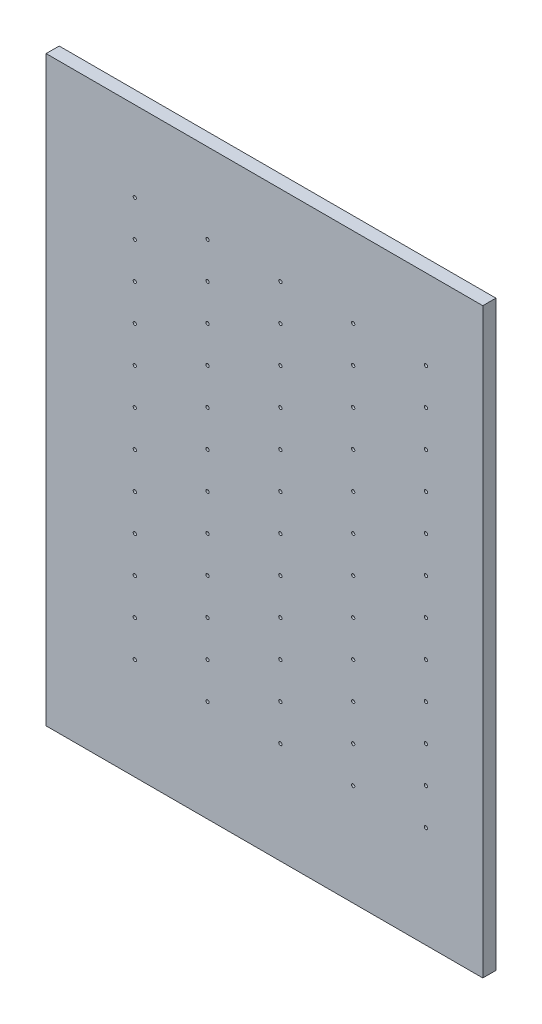
SolidWorks part; units mm, degrees
ref_plane "Спереди" through (0, 0, 0) normal (0, 0, 1) x (1, 0, 0)
ref_plane "Сверху" through (0, 0, 0) normal (0, 1, 0) x (1, 0, 0)
ref_plane "Справа" through (0, 0, 0) normal (1, 0, 0) x (0, 0, -1)
sketch "Эскиз1" plane through (0, 0, 0) normal (0, 0, 1) x (1, 0, 0)
  line L1 (0, 0) -> (600, 0)
  line L2 (0, 0) -> (0, 800)
  line L3 (0, 800) -> (600, 800)
  line L4 (600, 0) -> (600, 800)
extrude "Бобышка-Вытянуть1" add sketch "Эскиз1" along normal blind 18
sketch "Эскиз2" plane through (0, 0, 18) normal (0, 0, 1) x (1, 0, 0)
  circle A0 centre (521.8745, 139.7815) radius 2.25
  circle A1 centre (421.8745, 139.7815) radius 2.25
  circle A2 centre (321.8745, 139.7815) radius 2.25
  circle A3 centre (221.8745, 139.7815) radius 2.25
  circle A4 centre (121.8745, 139.7815) radius 2.25
  circle A5 centre (421.8745, 189.7815) radius 2.25
  circle A6 centre (321.8745, 189.7815) radius 2.25
  circle A7 centre (221.8745, 189.7815) radius 2.25
  circle A8 centre (121.8745, 189.7815) radius 2.25
  circle A9 centre (421.8745, 239.7815) radius 2.25
  circle A10 centre (321.8745, 239.7815) radius 2.25
  circle A11 centre (221.8745, 239.7815) radius 2.25
  circle A12 centre (121.8745, 239.7815) radius 2.25
  circle A13 centre (421.8745, 289.7815) radius 2.25
  circle A14 centre (321.8745, 289.7815) radius 2.25
  circle A15 centre (221.8745, 289.7815) radius 2.25
  circle A16 centre (121.8745, 289.7815) radius 2.25
  circle A17 centre (421.8745, 339.7815) radius 2.25
  circle A18 centre (321.8745, 339.7815) radius 2.25
  circle A19 centre (221.8745, 339.7815) radius 2.25
  circle A20 centre (121.8745, 339.7815) radius 2.25
  circle A21 centre (421.8745, 389.7815) radius 2.25
  circle A22 centre (321.8745, 389.7815) radius 2.25
  circle A23 centre (221.8745, 389.7815) radius 2.25
  circle A24 centre (121.8745, 389.7815) radius 2.25
  circle A25 centre (421.8745, 439.7815) radius 2.25
  circle A26 centre (321.8745, 439.7815) radius 2.25
  circle A27 centre (221.8745, 439.7815) radius 2.25
  circle A28 centre (121.8745, 439.7815) radius 2.25
  circle A29 centre (421.8745, 489.7815) radius 2.25
  circle A30 centre (321.8745, 489.7815) radius 2.25
  circle A31 centre (221.8745, 489.7815) radius 2.25
  circle A32 centre (121.8745, 489.7815) radius 2.25
  circle A33 centre (421.8745, 539.7815) radius 2.25
  circle A34 centre (321.8745, 539.7815) radius 2.25
  circle A35 centre (221.8745, 539.7815) radius 2.25
  circle A36 centre (121.8745, 539.7815) radius 2.25
  circle A37 centre (421.8745, 589.7815) radius 2.25
  circle A38 centre (321.8745, 589.7815) radius 2.25
  circle A39 centre (221.8745, 589.7815) radius 2.25
  circle A40 centre (121.8745, 589.7815) radius 2.25
  circle A41 centre (421.8745, 639.7815) radius 2.25
  circle A42 centre (321.8745, 639.7815) radius 2.25
  circle A43 centre (221.8745, 639.7815) radius 2.25
  circle A44 centre (121.8745, 639.7815) radius 2.25
  circle A45 centre (421.8745, 689.7815) radius 2.25
  circle A46 centre (321.8745, 689.7815) radius 2.25
  circle A47 centre (221.8745, 689.7815) radius 2.25
  circle A48 centre (121.8745, 689.7815) radius 2.25
  circle A49 centre (521.8745, 189.7815) radius 2.25
  circle A50 centre (521.8745, 239.7815) radius 2.25
  circle A51 centre (521.8745, 289.7815) radius 2.25
  circle A52 centre (521.8745, 339.7815) radius 2.25
  circle A53 centre (521.8745, 389.7815) radius 2.25
  circle A54 centre (521.8745, 439.7815) radius 2.25
  circle A55 centre (521.8745, 489.7815) radius 2.25
  circle A56 centre (521.8745, 539.7815) radius 2.25
  circle A57 centre (521.8745, 589.7815) radius 2.25
  circle A58 centre (521.8745, 639.7815) radius 2.25
  circle A59 centre (521.8745, 689.7815) radius 2.25
  dimension "D1" = 5
  dimension "D2" = 12
extrude "Вырез-Вытянуть1" cut sketch "Эскиз2" against normal blind 9
